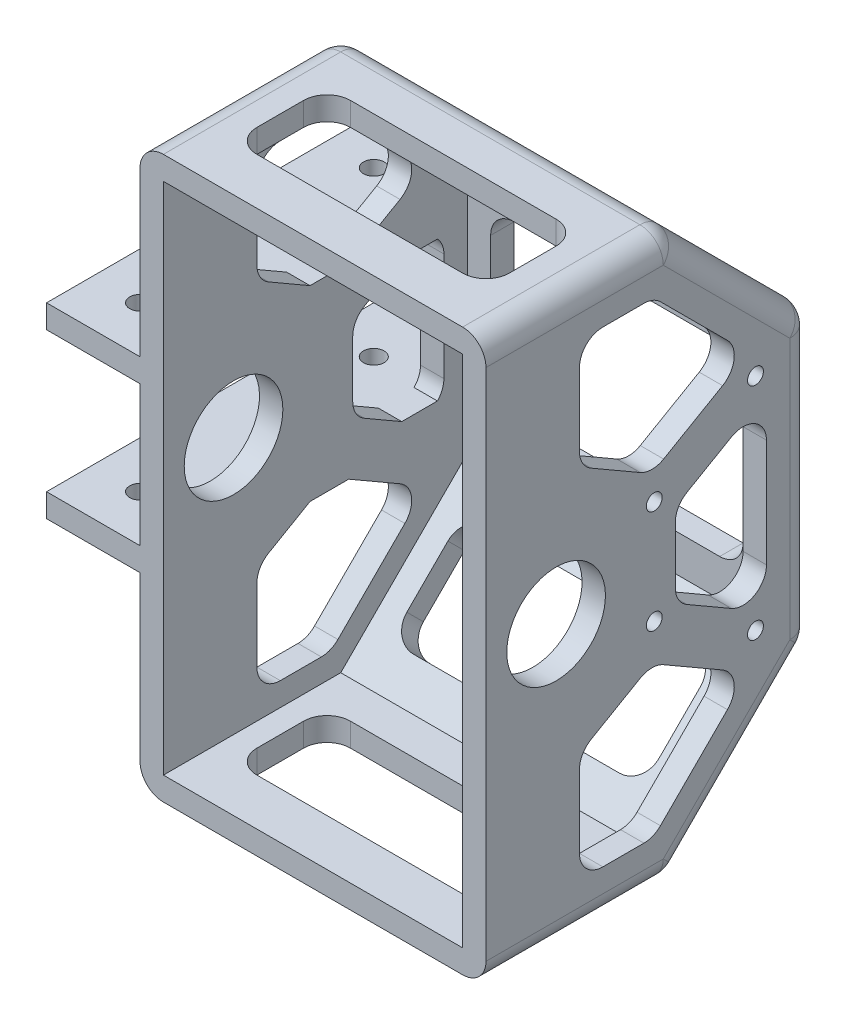
SolidWorks part; units mm, degrees
ref_plane "正面" through (0, 0, 0) normal (0, 0, 1) x (1, 0, 0)
ref_plane "平面" through (0, 0, 0) normal (0, 1, 0) x (1, 0, 0)
ref_plane "右側面" through (0, 0, 0) normal (1, 0, 0) x (0, 0, -1)
sketch "ｽｹｯﾁ1" plane through (0, 0, 0) normal (0, 0, 1) x (1, 0, 0)
  line L1 (-37, 60) -> (37, 60)
  line L2 (-37, 60) -> (-37, -60)
  line L3 (-37, -60) -> (37, -60)
  line L4 (37, 60) -> (37, -60)
  line L5 (-37, 60) -> (37, -60) construction
  line L6 (-37, -60) -> (37, 60) construction
  point P0 (0, 0)
  dimension "D1" = 120
  dimension "D2" = 74
extrude "ﾎﾞｽ - 押し出し1" add sketch "ｽｹｯﾁ1" along normal blind 70
chamfer "面取り2" distance 30 angle 45 2 edges at (0, 60, 0) (0, -60, 0)
sketch "ｽｹｯﾁ2" plane through (-37, 0, 0) normal (-1, 0, 0) x (0, 0, 1)
  line L0 (70, 60) -> (70, -60) construction
  line L1 (55, -23.6714) -> (55, -60)
  line L2 (55, 23.6714) -> (34.5, 11.8357)
  line L3 (34.5, 11.8357) -> (34.5, -11.8357)
  line L4 (34.5, -11.8357) -> (55, -23.6714)
  line L5 (55, -23.6714) -> (75.5, -11.8357)
  line L6 (75.5, -11.8357) -> (75.5, 11.8357)
  line L7 (75.5, 11.8357) -> (55, 23.6714)
  line L8 (70, -60) -> (30, -60) construction
  line L9 (34.5, -11.8357) -> (1.1122, -31.1122)
  line L10 (50, -23.6714) -> (50, -60)
  line L11 (0, -30) -> (30, -60) construction
  line L12 (55, 23.6714) -> (55, 60)
  line L13 (70, 60) -> (30, 60) construction
  line L14 (34.5, 11.8357) -> (1.1122, 31.1122)
  line L15 (30, 60) -> (0, 30) construction
  line L16 (32, -16.1658) -> (52.5, -28.0015)
  line L17 (32, -7.5056) -> (-1.3878, -26.782)
  line L18 (57.5, -28.0015) -> (80.5, -14.7224)
  line L19 (80.5, -14.7224) -> (80.5, 14.7224)
  line L20 (80.5, 14.7224) -> (57.5, 28.0015)
  line L21 (29.5, 11.8357) -> (29.5, -11.8357)
  line L22 (37, 16.1658) -> (3.6122, 35.4423)
  line L23 (52.5, 28.0015) -> (32, 16.1658)
  line L24 (60, 23.6714) -> (60, 60)
  line L25 (60, -23.6714) -> (60, -60)
  line L26 (37, -7.5056) -> (57.5, -19.3412)
  line L27 (37, -16.1658) -> (3.6122, -35.4423)
  line L28 (52.5, -19.3412) -> (70.5, -8.9489)
  line L29 (70.5, -8.9489) -> (70.5, 8.9489)
  line L30 (70.5, 8.9489) -> (52.5, 19.3412)
  line L31 (39.5, 11.8357) -> (39.5, -11.8357)
  line L32 (32, 7.5056) -> (-1.3878, 26.782)
  line L33 (57.5, 19.3412) -> (37, 7.5056)
  line L34 (50, 23.6714) -> (50, 60)
  line L47 (60, 50) -> (34.1421, 50)
  line L48 (34.1421, 50) -> (10, 25.8579)
  line L49 (10, 25.8579) -> (10, -25.8579)
  line L50 (10, -25.8579) -> (34.1421, -50)
  line L51 (34.1421, -50) -> (60, -50)
  line L52 (60, -50) -> (60, 50)
  line L53 (60, 50) -> (34.1421, 50)
  line L54 (34.1421, 50) -> (10, 25.8579)
  line L55 (10, 25.8579) -> (10, -25.8579)
  line L56 (10, -25.8579) -> (34.1421, -50)
  line L57 (34.1421, -50) -> (60, -50)
  line L58 (60, -50) -> (60, 50)
  circle A0 centre (55, 0) radius 10.55
  circle A1 centre (55, 0) radius 20.5 construction
  dimension "D1" = 21.1
  dimension "D2" = 15
  dimension "D3" = 41
  dimension "D4" = 5
  dimension "D5" = 5
  dimension "D6" = 10
shell "ｼｪﾙ1" thickness 5 removed face at (0, 0, 70)
extrude "ｶｯﾄ - 押し出し1" cut sketch "ｽｹｯﾁ2" against normal through all contours L56 L57 L10 L16 L27 | L32 L55 L17 L21 | L53 L54 L22 L23 L34 | L58 A0 | L58 A0 region at (-37, -34.4245, 35.5634) region at (-37, 0, 53.0651) region at (-37, 0, 62.2792) region at (-37, 34.4245, 35.5634) region at (-37, 0, 18.495)
sketch "ｽｹｯﾁ3" plane through (0, -15, -15) normal (0, -0.7071, -0.7071) x (1, 0, 0)
  line L8 (-27, 53.6396) -> (-27, 31.2132)
  line L9 (-27, 31.2132) -> (27, 31.2132)
  line L10 (27, 31.2132) -> (27, 53.6396)
  line L11 (27, 53.6396) -> (-27, 53.6396)
  line L12 (-27, 53.6396) -> (-27, 31.2132)
  line L13 (-27, 31.2132) -> (27, 31.2132)
  line L14 (27, 31.2132) -> (27, 53.6396)
  line L15 (27, 53.6396) -> (-27, 53.6396)
  dimension "D1" = 10
extrude "ｶｯﾄ - 押し出し2" cut sketch "ｽｹｯﾁ3" against normal blind 70
sketch "ｽｹｯﾁ4" plane through (0, 15, -15) normal (0, 0.7071, -0.7071) x (1, 0, 0)
  line L8 (27, -53.6396) -> (27, -31.2132)
  line L9 (27, -31.2132) -> (-27, -31.2132)
  line L10 (-27, -31.2132) -> (-27, -53.6396)
  line L11 (-27, -53.6396) -> (27, -53.6396)
  line L12 (27, -53.6396) -> (27, -31.2132)
  line L13 (27, -31.2132) -> (-27, -31.2132)
  line L14 (-27, -31.2132) -> (-27, -53.6396)
  line L15 (-27, -53.6396) -> (27, -53.6396)
  dimension "D1" = 10
extrude "ｶｯﾄ - 押し出し3" cut sketch "ｽｹｯﾁ4" against normal blind 70
sketch "ｽｹｯﾁ5" plane through (0, 0, 0) normal (0, 0, -1) x (-1, 0, 0)
  line L8 (27, -20) -> (27, 20)
  line L9 (27, 20) -> (-27, 20)
  line L10 (-27, 20) -> (-27, -20)
  line L11 (-27, -20) -> (27, -20)
  line L12 (27, -20) -> (27, 20)
  line L13 (27, 20) -> (-27, 20)
  line L14 (-27, 20) -> (-27, -20)
  line L15 (-27, -20) -> (27, -20)
  dimension "D1" = 10
extrude "ｶｯﾄ - 押し出し4" cut sketch "ｽｹｯﾁ5" against normal blind 70
sketch "ｽｹｯﾁ7" plane through (0, 60, 0) normal (0, 1, 0) x (1, 0, 0)
  line L8 (27, -60) -> (27, -40)
  line L9 (27, -40) -> (-27, -40)
  line L10 (-27, -40) -> (-27, -60)
  line L11 (-27, -60) -> (27, -60)
  line L12 (27, -60) -> (27, -40)
  line L13 (27, -40) -> (-27, -40)
  line L14 (-27, -40) -> (-27, -60)
  line L15 (-27, -60) -> (27, -60)
  dimension "D1" = 10
extrude "ｶｯﾄ - 押し出し5" cut sketch "ｽｹｯﾁ7" against normal through all
fillet "ﾌｨﾚｯﾄ1" radius 5 62 edges at (27, 51.1612, 24.6967) (-27, 51.1612, 24.6967) (-27, 35.3033, 8.8388) (27, 35.3033, 8.8388) (-27, 20, 2.5) (-27, -20, 2.5) (27, 20, 2.5) (27, -20, 2.5) (-27, -35.3033, 8.8388) (-27, -51.1612, 24.6967) (27, -51.1612, 24.6967) (27, -35.3033, 8.8388) (34.5, -50, 34.1421) (34.5, -29.596, 13.7382) (34.5, -17.6092, 34.5) (34.5, -26.5581, 50) (34.5, -50, 50) (34.5, 26.5581, 50) (34.5, 17.6092, 34.5) (34.5, 29.596, 13.7382) (34.5, 50, 34.1421) (34.5, 50, 50) (34.5, -20.2073, 10) (34.5, -8.9489, 29.5) (34.5, 8.9489, 29.5) (34.5, 20.2073, 10) (-34.5, 29.596, 13.7382) (-34.5, 50, 34.1421) (-34.5, 50, 50) (-34.5, 26.5581, 50) (-34.5, 17.6092, 34.5) (-34.5, 20.2073, 10) (-34.5, 8.9489, 29.5) (-34.5, -20.2073, 10) (-34.5, -8.9489, 29.5) (-34.5, -29.596, 13.7382) (-34.5, -17.6092, 34.5) (-34.5, -26.5581, 50) (-34.5, -50, 50) (-34.5, -50, 34.1421) (-27, -57.5, 60) (-27, -57.5, 40) (27, -57.5, 40) (27, -57.5, 60) (27, 57.5, 60) (27, 57.5, 40) (-27, 57.5, 40) (-27, 57.5, 60) (37, -45, 15) (37, -60, 50) (-37, -60, 50) (-37, -45, 15) (0, -30, 0) (-37, 0, 0) (-37, 45, 15) (0, 60, 30) (-37, 60, 50) (37, 60, 50) (0, 30, 0) (37, 45, 15) (37, 0, 0) (0, -60, 30)
sketch "ｽｹｯﾁ10" plane through (-37, 0, 0) normal (-1, 0, 0) x (0, 0, 1)
  line L0 (5, 27.9289) -> (5, -27.9289) construction
  line L1 (70, 17.5) -> (5, 17.5)
  line L2 (70, 17.5) -> (70, -17.5)
  line L3 (70, -17.5) -> (5, -17.5)
  line L4 (5, 17.5) -> (5, -17.5)
  line L5 (70, 17.5) -> (5, -17.5) construction
  line L6 (70, -17.5) -> (5, 17.5) construction
  line L7 (70, 55) -> (70, -55) construction
  line L8 (70, -15) -> (5, -15)
  line L9 (70, 20) -> (5, 20)
  line L10 (70, -20) -> (5, -20)
  line L11 (70, 15) -> (5, 15)
  line L13 (5, -15) -> (0, -15)
  line L14 (5, -15) -> (5, -20)
  line L15 (5, -20) -> (0, -20)
  line L16 (0, -15) -> (0, -20)
  line L17 (2.5, -20) -> (2.5, -15) construction
  line L18 (5, -17.5) -> (0, -17.5) construction
  line L19 (5, 20) -> (0, 20)
  line L20 (5, 20) -> (5, 15)
  line L21 (5, 15) -> (0, 15)
  line L22 (0, 20) -> (0, 15)
  line L23 (2.5, 15) -> (2.5, 20) construction
  line L24 (5, 17.5) -> (0, 17.5) construction
  circle A0 centre (55, 0) radius 10.55 construction
  point P0 (37.5, 0)
  point P110 (2.5, -17.5)
  point P114 (2.5, 17.5)
  line M12 (47.5, 25.1147) -> (37, 19.0526)
  arc M13 (37, 19.0526) -> (32, 19.0526) centre (34.5, 23.3827) cw
  line M14 (32, 19.0526) -> (19.3813, 26.338)
  arc M17 (10, 11.547) -> (17.5, 15.8771) centre (15, 11.547) cw
  line M18 (17.5, 15.8771) -> (27, 10.3923)
  line M22 (27, -10.3923) -> (17.5, -15.8771)
  arc M23 (17.5, -15.8771) -> (10, -11.547) centre (15, -11.547) cw
  line M28 (19.3813, -26.338) -> (32, -19.0526)
  arc M29 (32, -19.0526) -> (37, -19.0526) centre (34.5, -23.3827) cw
  line M30 (37, -19.0526) -> (47.5, -25.1147)
  line M36 (70, -55) -> (70, 55)
  line M39 (5, 27.9289) -> (5, -27.9289)
  dimension "D1" = 0
  dimension "D2" = 35
  dimension "D3" = 0
  dimension "D4" = 2.5
  dimension "D5" = 2.5
extrude "ﾎﾞｽ - 押し出し3" add sketch "ｽｹｯﾁ10" along normal blind 20 and the other way blind 5 contours L8 L4 L3 M36 M22 M23 | L10 L3 M36 M39 M28 M29 M30 | L11 L1 M36 M39 M17 M18 | L9 L1 M36 M12 M13 M14 M39 | L10 M30 M29 M28 | L9 M12 M14 M13 | L8 M22 M23 | L11 M18 M17 | L19 L22 L21 M39 | L13 L16 L15 L4 M39 region at (-37, 16.2819, 38.6398) region at (-37, 18.7162, 37.6667) region at (-37, 17.5, 2.5) region at (-37, -16.2819, 38.6398) region at (-37, 15.6213, 15.0573) region at (-37, 19.3583, 34.5) region at (-37, -17.5, 2.5) region at (-37, -18.7162, 37.6667) region at (-37, -15.6213, 15.0573) region at (-37, -19.3583, 34.5)
sketch "ｽｹｯﾁ12" plane through (0, -20, 0) normal (0, -1, 0) x (1, 0, 0)
  line L0 (-57, 70) -> (-57, 0) construction
  line L1 (-37, 70) -> (-57, 70) construction
  line L2 (-57, 70) -> (-57, 0) construction
  circle A0 centre (-47, 60) radius 2.2
  circle A1 centre (-47, 10) radius 2.2
  dimension "D1" = 10
  dimension "D2" = 10
  dimension "D3" = 4.4
  dimension "D4" = 50
  dimension "D5" = 4.4
  dimension "D6" = 10
extrude "ｶｯﾄ - 押し出し7" cut sketch "ｽｹｯﾁ12" against normal through all
sketch "ｽｹｯﾁ13" plane through (37, 0, 0) normal (1, 0, 0) x (0, 0, -1)
  line L0 (-34, -10.0111) -> (-12.3494, -22.5111) construction
  line L1 (-34, -10.0111) -> (-34, 12.1244) construction
  line L2 (-34, 12.1244) -> (-12.3494, 24.6244) construction
  line L3 (-12.3494, 24.6244) -> (-12.3494, -22.5111) construction
  circle A0 centre (-12.3494, 24.6244) radius 1.7
  circle A1 centre (-34, 12.1244) radius 1.7
  circle A2 centre (-34, -10.0111) radius 1.7
  circle A3 centre (-12.3494, -22.5111) radius 1.7
  dimension "D1" = 3.4
  dimension "D2" = 3.4
  dimension "D3" = 3.4
  dimension "D4" = 3.4
extrude "ｶｯﾄ - 押し出し8" cut sketch "ｽｹｯﾁ13" against normal blind 10
